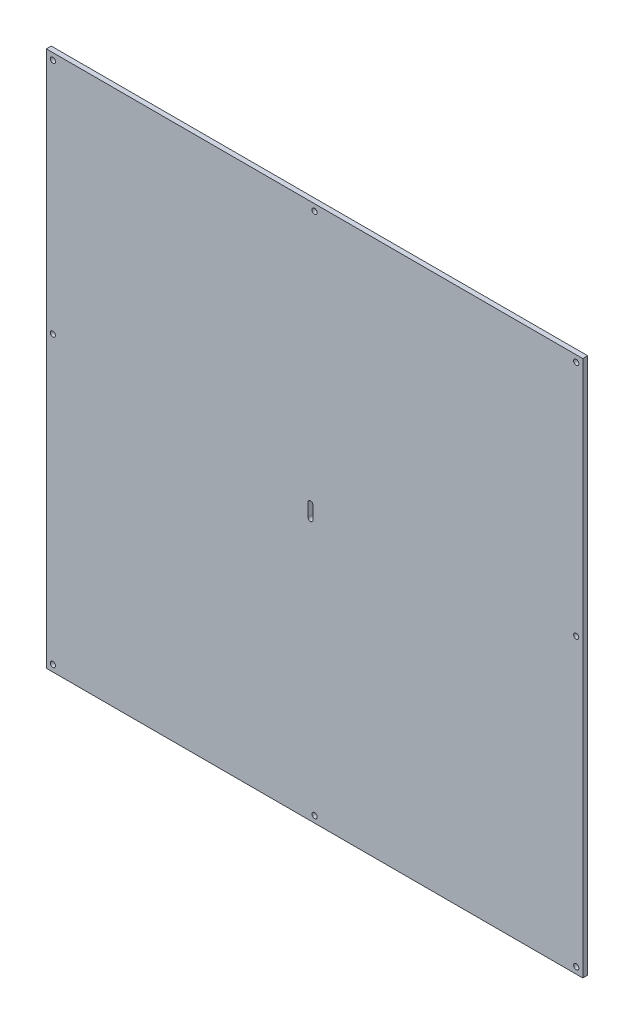
SolidWorks part; units mm, degrees
ref_plane "Alzado" through (0, 0, 0) normal (0, 0, 1) x (1, 0, 0)
ref_plane "Planta" through (0, 0, 0) normal (0, 1, 0) x (1, 0, 0)
ref_plane "Vista lateral" through (0, 0, 0) normal (1, 0, 0) x (0, 0, -1)
sketch "Croquis1" plane through (0, 0, 0) normal (0, 0, 1) x (1, 0, 0)
  line L1 (0, 0) -> (328, 0)
  line L2 (0, 0) -> (0, 328)
  line L3 (0, 328) -> (328, 328)
  line L4 (328, 0) -> (328, 328)
  dimension "D1" = 328
  dimension "D2" = 328
extrude "Saliente-Extruir1" add sketch "Croquis1" along normal blind 3
sketch "Croquis2" plane through (0, 0, 3) normal (0, 0, 1) x (1, 0, 0)
  line L0 (328, 328) -> (0, 328) construction
  line L1 (0, 328) -> (0, 0) construction
  line L2 (0, 164) -> (328, 164) construction
  line L3 (328, 0) -> (328, 328) construction
  circle A0 centre (4, 324) radius 1.6
  circle A1 centre (164, 324) radius 1.6
  circle A2 centre (324, 324) radius 1.6
  circle A3 centre (324, 4) radius 1.6
  circle A4 centre (164, 4) radius 1.6
  circle A5 centre (4, 4) radius 1.6
  dimension "D1" = 3.2
  dimension "D2" = 4
  dimension "D3" = 4
  dimension "D4" = 160
  dimension "D5" = 160
extrude "Cortar-Extruir1" cut sketch "Croquis2" against normal up to surface (3 mm away) up to face at (164, 164, 0)
sketch "Croquis3" plane through (0, 0, 3) normal (0, 0, 1) x (1, 0, 0)
  line L0 (4, 324) -> (4, 4) construction
  line L1 (324, 4) -> (324, 324) construction
  circle A2 centre (4, 179) radius 1.55
  circle A4 centre (324, 179) radius 1.55
  point P6 (324, 179)
  dimension "D1" = 3.1
  dimension "D3" = 3.1
  dimension "D2" = 175
extrude "Cortar-Extruir2" cut sketch "Croquis3" against normal up to surface (3 mm away) up to face at (2.4, 4, 0)
sketch "Croquis4" plane through (0, 0, 3) normal (0, 0, 1) x (1, 0, 0)
  line L0 (161.5, 168) -> (161.5, 160) construction
  line L1 (163, 168) -> (163, 160)
  line L2 (160, 168) -> (160, 160)
  line L3 (0, 328) -> (0, 0) construction
  line L4 (0, 0) -> (328, 0) construction
  arc A0 (163, 168) -> (160, 168) centre (161.5, 168) ccw
  arc A1 (160, 160) -> (163, 160) centre (161.5, 160) ccw
  point P2 (161.5, 164)
  dimension "D1" = 8
  dimension "D2" = 3
  dimension "D3" = 160
  dimension "D4" = 160
extrude "Cortar-Extruir3" cut sketch "Croquis4" against normal up to surface (3 mm away) up to face at (2.45, 179, 0)
